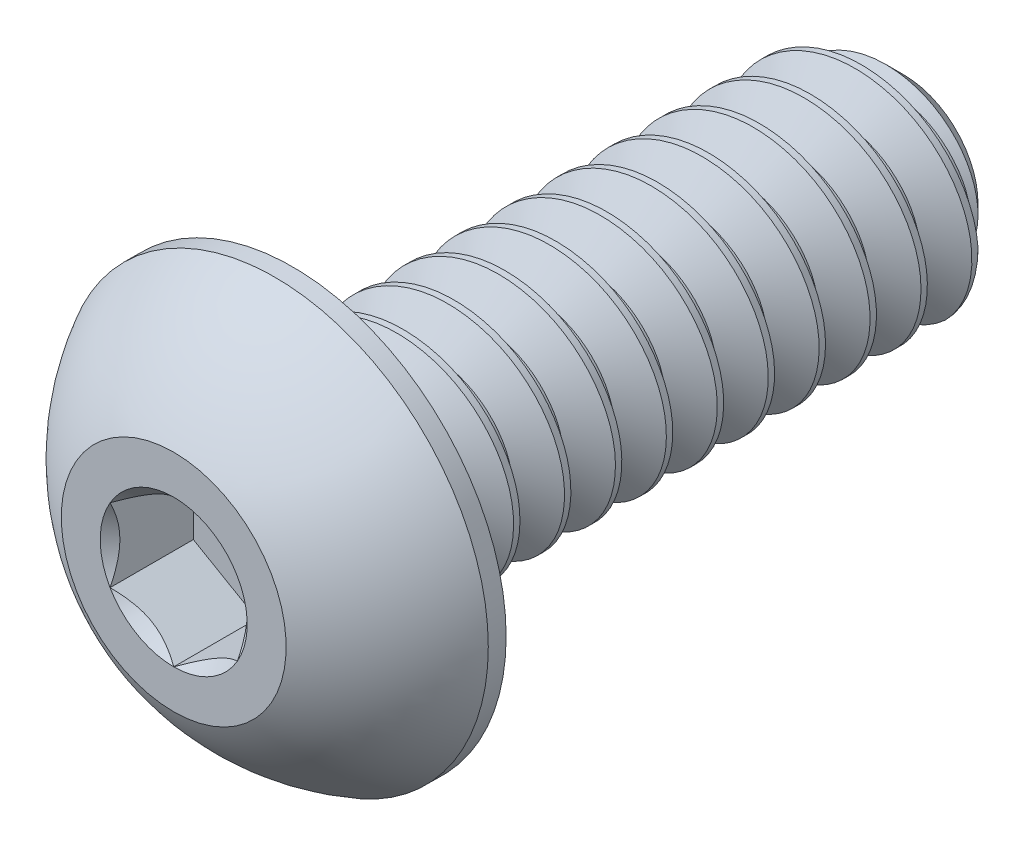
SolidWorks part; units mm, degrees
ref_plane "Front" through (0, 0, 0) normal (0, 0, 1) x (1, 0, 0)
ref_plane "Top" through (0, 0, 0) normal (0, 1, 0) x (1, 0, 0)
ref_plane "Right" through (0, 0, 0) normal (1, 0, 0) x (0, 0, -1)
sketch "Sketch1" plane through (0, 0, 0) normal (1, 0, 0) x (0, 0, -1)
  line L2 (1.8542, 1.7526) -> (11.3792, 1.7526)
  line L3 (11.3792, 1.7526) -> (11.3792, 0)
  line L4 (11.3792, 0) -> (1.8542, 0)
  line L6 (1.5761, 3.3274) -> (1.8542, 3.3274) construction
  line L7 (11.3792, 1.7526) -> (11.3792, -1.7526) construction
  line L8 (0, 0) -> (1.8542, 0) construction
  line L9 (1.8542, 3.3274) -> (1.8542, -3.3274) construction
  line L11 (1.8542, 1.7526) -> (1.8542, 0)
  line L13 (0, 0.9922) -> (0, -0.9922) construction
  line L14 (0, 0.9922) -> (0, 1.7526) construction
  arc A3 (0, 1.7526) -> (1.5761, 3.3274) centre (3.326, 0) cw construction
  dimension "D1" = 0.2781
revolve "Revolve1" add sketch "Sketch1" angle 360 mid plane about L4
sketch "Sketch3" plane through (0, 0, -11.3792) normal (0, 0, -1) x (-1, 0, 0)
  circle A0 centre (0, 0) radius 1.7526
curve "Helix/Spiral1" pitch 0.7937 height 10.3188 turns 13
sketch "Sketch2" plane through (0, 0, 0) normal (1, 0, 0) x (0, 0, -1)
  line L0 (11.3792, 1.7526) -> (12.0737, 1.7526)
  line L1 (12.0737, 1.7526) -> (11.7761, 1.237)
  line L2 (11.7761, 1.237) -> (11.6769, 1.237)
  line L3 (11.6769, 1.237) -> (11.3792, 1.7526)
  line L4 (11.528, 1.4948) -> (11.9249, 1.4948) construction
  dimension "D1" = 60
  dimension "D2" = 0.0992
  dimension "D3" = 0.3969
chamfer "Chamfer1" distance 0.5953 angle 45 1 edges at (0, 1.7526, -11.3792)
sweep "Cut-Sweep1" cut profiles "Sketch2" path "Helix/Spiral1" align with end faces yes
sketch "Sketch7" plane through (0, 0, 0) normal (1, 0, 0) x (0, 0, -1)
  line L6 (1.5761, 3.3274) -> (1.8542, 3.3274) construction
  line L8 (0, 0) -> (1.8542, 0) construction
  line L11 (1.8542, 3.3274) -> (1.8542, -3.3274) construction
  line L12 (1.5761, 3.3274) -> (1.8542, 3.3274)
  line L13 (0, 0) -> (1.8542, 0)
  line L14 (0, 0.9922) -> (0, -0.9922) construction
  line L15 (1.8542, 3.3274) -> (1.8542, 0)
  line L16 (0, 1.7526) -> (0, 0)
  arc A2 (1.5761, 3.3274) -> (0, 1.7526) centre (3.326, 0) ccw construction
  arc A3 (1.5761, 3.3274) -> (0, 1.7526) centre (3.326, 0) ccw
revolve "Revolve2" add sketch "Sketch7" angle 360 mid plane about L13
sketch "Sketch5" plane through (0, 0, 0) normal (0, 0, 1) x (1, 0, 0)
  line L1 (0.9922, -0.5728) -> (0.9922, 0.5728)
  line L2 (0.9922, 0.5728) -> (0, 1.1457)
  line L3 (0, 1.1457) -> (-0.9922, 0.5728)
  line L4 (-0.9922, 0.5728) -> (-0.9922, -0.5728)
  line L5 (-0.9922, -0.5728) -> (0, -1.1457)
  line L6 (0, -1.1457) -> (0.9922, -0.5728)
  circle A0 centre (0, 0) radius 0.9922 construction
extrude "Cut-Extrude2" cut sketch "Sketch5" against normal blind 1.2979
sketch "Sketch6" plane through (0, 0, 0) normal (0, 0, 1) x (1, 0, 0)
  circle A0 centre (0, 0) radius 1.1457
extrude "Cut-Extrude3" cut sketch "Sketch6" against normal blind 1.2979 draft 45
sketch "Sketch9" [suppressed] plane through (0, 0, -1.4986) normal (0, 0, 1) x (1, 0, 0)
  circle A2 centre (0, 0) radius 1.4224
extrude "Boss-Extrude2" [suppressed] add sketch "Sketch9" against normal offset from surface (12.7 mm away) 31.75
sketch "Sketch10" plane through (0, 0, 0) normal (1, 0, 0) x (0, 0, -1)
  line L0 (11.3792, 1.7526) -> (11.3792, -1.7526) construction
  point P0 (10.1886, -1.7526)
  dimension "D1" = 1.1906
equation "\"D3@Helix/Spiral1\" = \"Lg@Sketch1\" + \"D4@Helix/Spiral1\""
equation "\"D2@Sketch2\" = \"D4@Helix/Spiral1\" * .125"
equation "\"D3@Sketch2\" = \"D4@Helix/Spiral1\" * .5"
equation "\"D1@Chamfer1\" = \"D4@Helix/Spiral1\" * .75"
equation "\"D1@Cut-Extrude2\" = \"Head Ht@Sketch1\" * .7"
equation "\"D1@Sketch1\" = \"Head Ht@Sketch1\" * .15"
equation "\"D1@Sketch10\" = \"D4@Helix/Spiral1\" * 1.5"
equation "\"D1@Cut-Extrude3\" = \"D1@Cut-Extrude2\""
